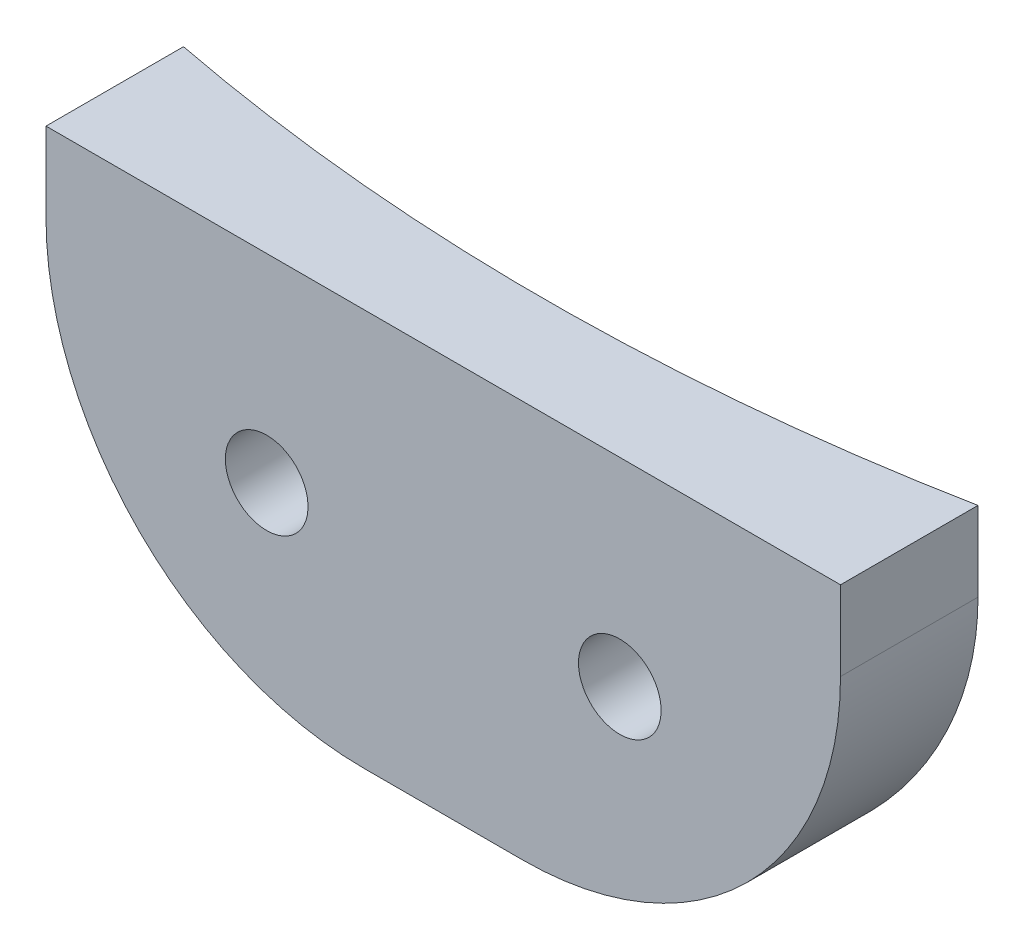
SolidWorks part; units mm, degrees
material "6061 Alloy"
ref_plane "Front Plane" through (0, 0, 0) normal (0, 0, 1) x (1, 0, 0)
ref_plane "Top Plane" through (0, 0, 0) normal (0, 1, 0) x (1, 0, 0)
ref_plane "Right Plane" through (0, 0, 0) normal (1, 0, 0) x (0, 0, -1)
sketch "Sketch1" plane through (0, 0, 0) normal (0, 1, 0) x (1, 0, 0)
  line L0 (-12.7, -65.4543) -> (-12.7, -68.6858)
  line L1 (12.7, -65.4543) -> (12.7, -68.6858)
  line L2 (-12.7, -69.85) -> (12.7, -69.85)
  line L3 (-12.7, -68.6858) -> (-12.7, -69.85)
  line L4 (12.7, -68.6858) -> (12.7, -69.85)
  circle A0 centre (0, 0) radius 66.675
  circle A1 centre (0, 0) radius 69.85
  dimension "D1" = 133.35
  dimension "D3" = 12.7
  dimension "D4" = 12.7
  dimension "D2" = 3.175
extrude "Boss-Extrude1" add sketch "Sketch1" along normal blind 12.7 contours L0 A1 L1 A0 | A1 L3 L2 | A1 L2 L4 region at (0, 0, 67.8645) region at (-9.5303, 0, 69.5012) region at (9.5303, 0, 69.5012)
sketch "Sketch2" plane through (0, 0, 0) normal (0, 0, 1) x (1, 0, 0)
  line L0 (0, 12.7) -> (0, 0) construction
  line L5 (-12.7, 0) -> (12.7, 0)
  line L6 (12.7, 0) -> (12.7, 12.7)
  line L7 (12.7, 12.7) -> (-12.7, 12.7)
  line L12 (-12.7, 12.7) -> (-12.7, 0)
  line L13 (-12.7, 0) -> (12.7, 0)
  line L14 (12.7, 0) -> (12.7, 12.7)
  line L15 (12.7, 12.7) -> (-12.7, 12.7)
  line L16 (-12.7, 12.7) -> (-12.7, 0)
  circle A0 centre (-5.6444, 6.35) radius 1.3208
  dimension "D6" = 2.6416
  dimension "D5" = 5.6444
  dimension "D2" = 6.35
extrude "Cut-Extrude1" cut sketch "Sketch2" along normal up to surface (69.85 mm away) contours A0 up to face at (0, 6.35, 69.85)
mirror "Mirror1" about plane through (0, 0, 0) normal (1, 0, 0) of "Cut-Extrude1"
sketch "Sketch3" plane through (0, 0, 0) normal (0, 0, 1) x (1, 0, 0)
  line L0 (-12.7, 12.7) -> (-12.7, 0)
  line L6 (-12.7, 0) -> (0, 0)
  line L7 (12.7, 12.7) -> (12.7, 0)
  line L8 (-2.54, 0) -> (2.54, 0)
  line L9 (12.7, 10.16) -> (12.7, 12.7)
  line L10 (12.7, 12.7) -> (-12.7, 12.7)
  line L11 (-12.7, 12.7) -> (-12.7, 10.16)
  line L12 (12.7, 0) -> (2.54, 0)
  arc A0 (2.54, 0) -> (12.7, 10.16) centre (2.54, 10.16) ccw
  arc A1 (-2.54, 0) -> (-12.7, 10.16) centre (-2.54, 10.16) cw
  dimension "D2" = 10.16
  dimension "D6" = 2.54
  dimension "D1" = 12.7
  dimension "D3" = 12.7
  dimension "D4" = 2.54
  dimension "D5" = 2.54
  dimension "D7" = 2.54
  dimension "D8" = 2.54
  dimension "D9" = 10.16
extrude "Cut-Extrude2" cut sketch "Sketch3" along normal up to surface (69.85 mm away) contours L6 A1 L0 | A0 L12 L7 region at (-10.4306, 2.2694, 0) region at (10.4306, 2.2694, 0) up to face at (4.3236, 6.35, 69.85)
equation "\"Middle Coupler Inner Daimeter\"= 4.75in"
equation "\"Middle Coupler  Wall Thickness\" = 0.25in"
equation "\"Middle Coupler Bottom Thickness\"= 0.2in"
equation "\"Bearing Rail Offset\"= 0.45in"
equation "\"3-56 UNF Tap\"= 0.089in"
equation "\"3-56 UNF Clearance\"= 0.104in"
equation "\"Ball Bearing Distance\"= 0.03in"
equation "\"TCA Outer Diameter\" = 6.625in"
equation "\"D1@Sketch1\"=\"Middle Coupler Inner Daimeter\"+0.5"
equation "\"D2@Sketch1\"=1/8"
equation "\"D3@Sketch1\"=0.5"
equation "\"D4@Sketch1\"=\"D3@Sketch1\""
equation "\"D6@Sketch2\"=\"3-56 UNF Clearance\""
equation "\"Interstage Aeroframe Wall Thickness\" = 0.072in"
equation "\"Compression Spring OD\"= 0.42in"
equation "\"10-24 Tap\"= 0.157in"
equation "\"10-24 Clearance\"= 0.196in"
equation "\"Lower Stage Fuselage Wall Thickness\" = 0.25in"
equation "\"6-32 Tap\" = 0.107in"
equation "\"1/4-20 Tap\" = 0.201in"
